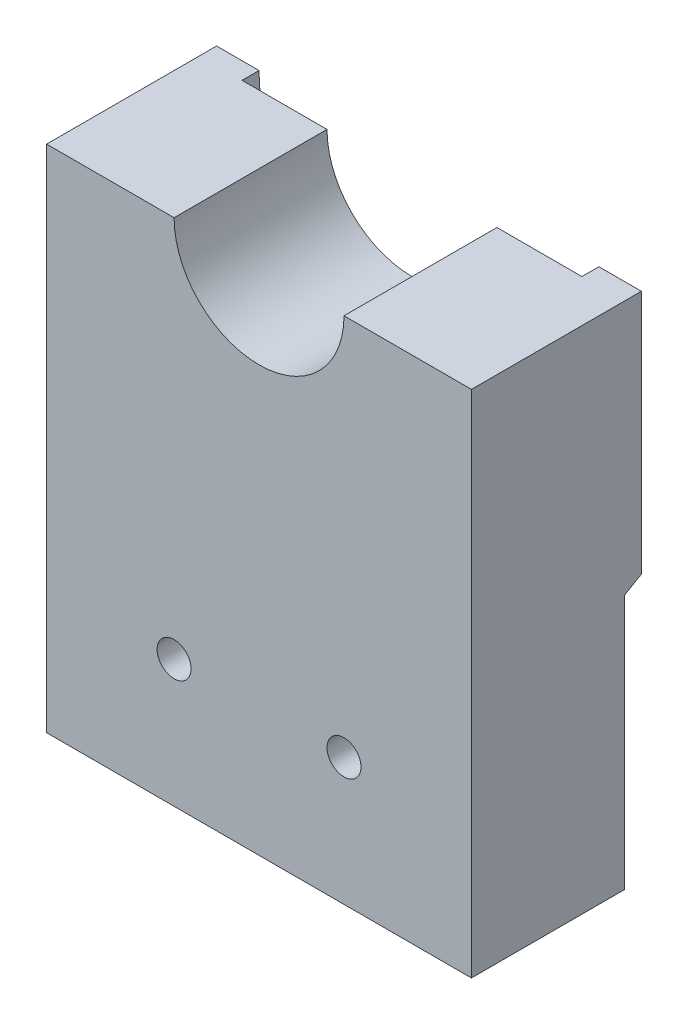
SolidWorks part; units mm, degrees
material "Mahogany"
ref_plane "Plan de face" through (0, 0, 0) normal (0, 0, 1) x (1, 0, 0)
ref_plane "Plan de dessus" through (0, 0, 0) normal (0, 1, 0) x (1, 0, 0)
ref_plane "Plan de droite" through (0, 0, 0) normal (1, 0, 0) x (0, 0, -1)
sketch "Sketch1" plane through (0, 0, 0) normal (0, 0, 1) x (1, 0, 0)
  line L1 (0, 0) -> (25, 0)
  line L2 (0, 0) -> (0, 30)
  line L3 (0, 30) -> (25, 30)
  line L4 (25, 0) -> (25, 30)
  dimension "D1" = 25
  dimension "D2" = 30
extrude "Boss-Extrude1" add sketch "Sketch1" along normal blind 10
sketch "Sketch2" plane through (25, 0, 0) normal (1, 0, 0) x (0, 0, -1)
  line L0 (0, 15.5774) -> (-1, 15)
  line L1 (0, 0) -> (0, 30) construction
  line L2 (-1, 15) -> (-1, 0)
  line L3 (-10, 0) -> (0, 0) construction
  line L4 (-10, 0) -> (-10, 30) construction
  line L5 (-10, 15) -> (0, 15) construction
  line L6 (-1, 0) -> (0, 0)
  line L7 (0, 0) -> (0, 15.5774)
  dimension "D1" = 9
  dimension "D2" = 120
extrude "Cut-Extrude1" cut sketch "Sketch2" against normal through all
sketch "Sketch3" plane through (0, 0, 0) normal (0, 0, -1) x (-1, 0, 0)
  line L0 (-25, 30) -> (0, 30) construction
  line L1 (-22.5, 30) -> (-2.5, 30)
  arc A0 (-22.5, 30) -> (-2.5, 30) centre (-12.5, 30) ccw
  dimension "D1" = 20
extrude "Cut-Extrude2" cut sketch "Sketch3" against normal up to surface (1 mm away) up to face at (12.5, 7.5, 1)
sketch "Sketch4" plane through (0, 0, 1) normal (0, 0, -1) x (-1, 0, 0)
  line L0 (-2.5, 30) -> (-22.5, 30) construction
  line L1 (-7.5, 30) -> (-17.5, 30)
  arc A0 (-17.5, 30) -> (-7.5, 30) centre (-12.5, 30) ccw
  dimension "D1" = 10
extrude "Cut-Extrude3" cut sketch "Sketch4" against normal through all
sketch "Sketch5" plane through (0, 0, 1) normal (0, 0, -1) x (-1, 0, 0)
  line L0 (-25, 7.5) -> (0, 7.5) construction
  line L3 (-25, 15) -> (-25, 0) construction
  line L4 (0, 15) -> (0, 0) construction
  line L5 (-12.5, 0) -> (-12.5, 15) construction
  line L6 (0, 0) -> (-25, 0) construction
  line L7 (0, 15) -> (-25, 15) construction
  circle A0 centre (-17.5, 7.5) radius 1
  circle A1 centre (-7.5, 7.5) radius 1
  dimension "D2" = 2
  dimension "D1" = 5
extrude "Cut-Extrude5" cut sketch "Sketch5" against normal through all
